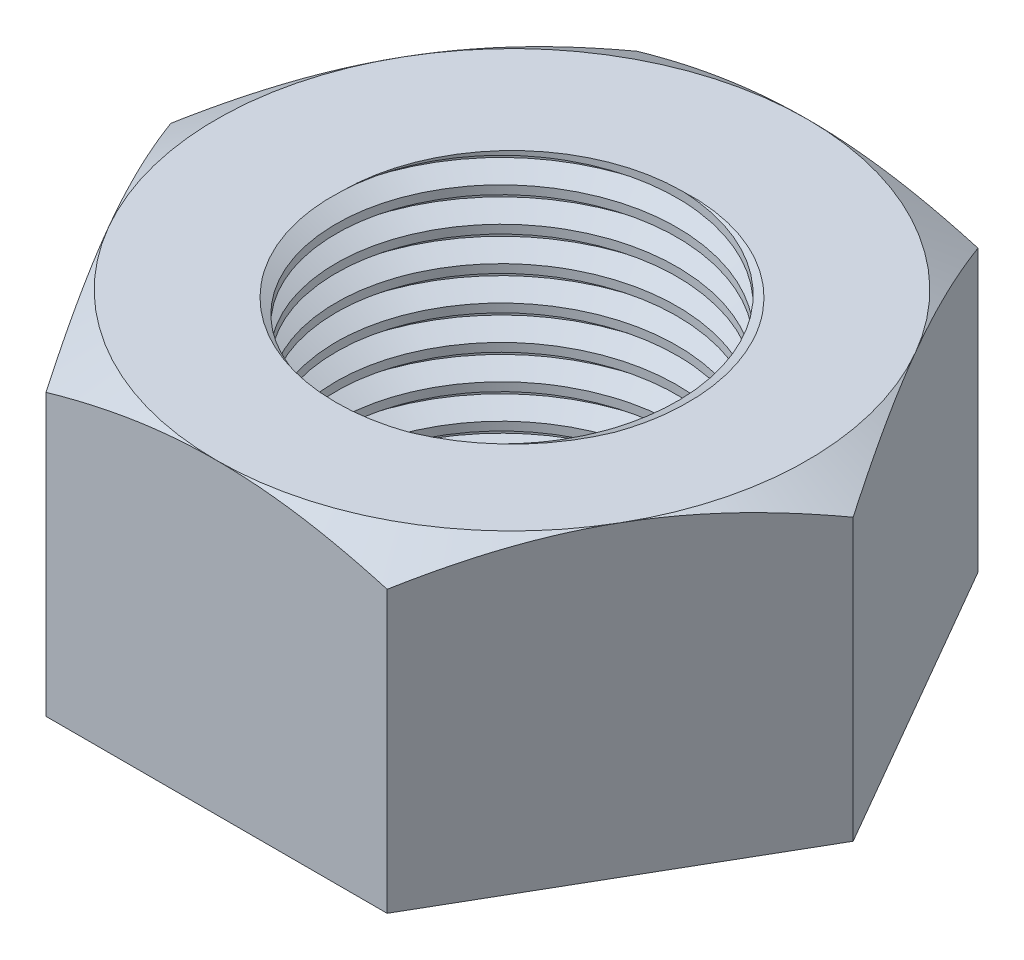
SolidWorks part; units mm, degrees
ref_plane "Front Plane" through (0, 0, 0) normal (0, 0, 1) x (1, 0, 0)
ref_plane "Top Plane" through (0, 0, 0) normal (0, 1, 0) x (1, 0, 0)
ref_plane "Right Plane" through (0, 0, 0) normal (1, 0, 0) x (0, 0, -1)
sketch "Sketch1" plane through (0, 0, 0) normal (0, 1, 0) x (1, 0, 0)
  line L1 (10, -17.3205) -> (20, 0)
  line L2 (20, 0) -> (10, 17.3205)
  line L3 (10, 17.3205) -> (-10, 17.3205)
  line L4 (-10, 17.3205) -> (-20, 0)
  line L5 (-20, 0) -> (-10, -17.3205)
  line L6 (-10, -17.3205) -> (10, -17.3205)
  circle A0 centre (0, 0) radius 17.3205 construction
  dimension "D1" = 40
extrude "Boss-Extrude1" add sketch "Sketch1" along normal blind 18
sketch "Sketch2" plane through (0, 0, 0) normal (1, 0, 0) x (0, 0, -1)
  line L0 (0, 0) -> (0, -50000) construction
  line L1 (17.3205, 18) -> (20.7846, 18)
  line L2 (20.7846, 18) -> (20.7846, 16)
  line L3 (20.7846, 16) -> (17.3205, 18)
  dimension "D1" = 30
  dimension "D2" = 2
revolve "Cut-Revolve1" cut sketch "Sketch2" angle 360 about L0
sketch "Sketch3" plane through (0, 18, 0) normal (0, 1, 0) x (1, 0, 0)
  circle A0 centre (0, 0) radius 10
  dimension "D1" = 20
extrude "Cut-Extrude1" cut sketch "Sketch3" against normal through all both and the other way through all
thread "Thread1" pitch 2 method cut profile "Thread Profile1" start angle 0, offset 4, length 0, pitch 2, diameter 20
ref_plane "Plane1" through (-10, 22, 0) normal (0, 0, 1) x (-1, 0, 0)
sketch "Thread Profile1" plane through (-10, 22, 0) normal (0, 0, 1) x (-1, 0, 0)
  line L0 (0, 0) -> (0, 2) construction
  line L1 (0, 0) -> (1.0825, 0.625)
  line L2 (1.0825, 0.625) -> (1.0825, 0.875)
  line L3 (1.0825, 0.875) -> (0, 1.5)
  line L4 (1.0825, 0.75) -> (0, 0.75) construction
  line L11 (0, 0) -> (0, 1.5)
  point P2 (0, 0)
  dimension "Pitch" = 2
  dimension "Profile_Angle" = 60
  dimension "Profile_Land" = 0.25
  dimension "Profile_Height" = 1.0825
